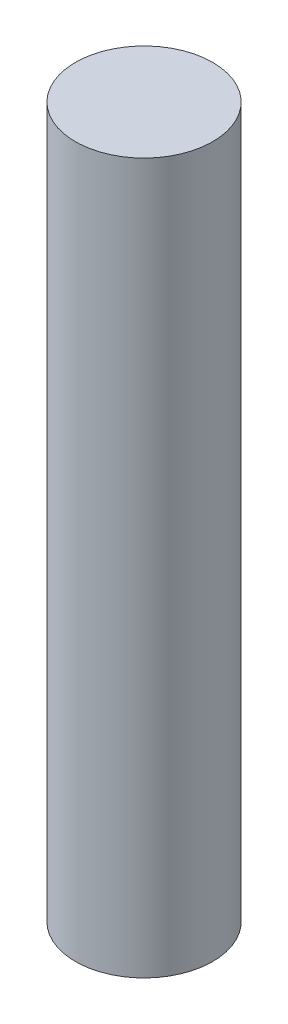
SolidWorks part; units mm, degrees
material "6061-T6 (SS)"
ref_plane "Front Plane" through (0, 0, 0) normal (0, 0, 1) x (1, 0, 0)
ref_plane "Top Plane" through (0, 0, 0) normal (0, 1, 0) x (1, 0, 0)
ref_plane "Right Plane" through (0, 0, 0) normal (1, 0, 0) x (0, 0, -1)
sketch "Sketch1" plane through (0, 0, 0) normal (0, 1, 0) x (1, 0, 0)
  circle A0 centre (0, 0) radius 4
  dimension "D1" = 8
extrude "Boss-Extrude1" add sketch "Sketch1" along normal mid plane 41.35
